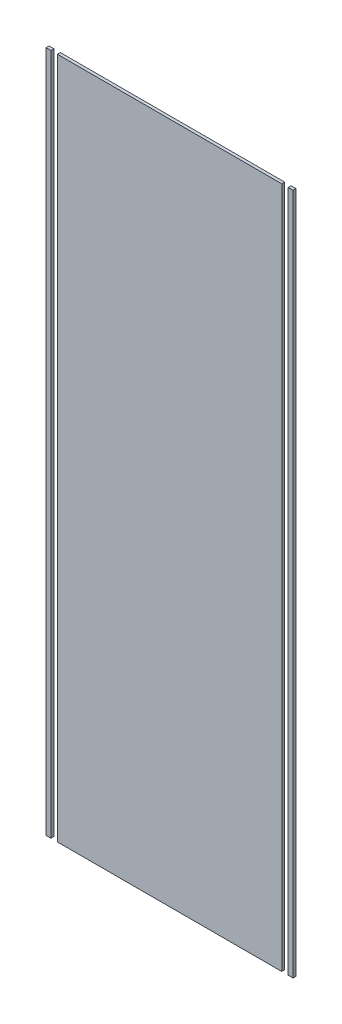
SolidWorks part; units mm, degrees
ref_plane "Спереди" through (0, 0, 0) normal (0, 0, 1) x (1, 0, 0)
ref_plane "Сверху" through (0, 0, 0) normal (0, 1, 0) x (1, 0, 0)
ref_plane "Справа" through (0, 0, 0) normal (1, 0, 0) x (0, 0, -1)
sketch "Эскиз1" plane through (0, 0, 0) normal (0, 0, 1) x (1, 0, 0)
  line L0 (1138.3, 447) -> (518, 447) construction
  line L1 (573.5, -949) -> (583.5, -949)
  line L2 (573.5, -949) -> (573.5, 447)
  line L3 (573.5, 447) -> (583.5, 447)
  line L4 (583.5, -949) -> (583.5, 447)
  line L5 (1068.8, -949) -> (1078.8, -949)
  line L6 (1068.8, -949) -> (1068.8, 447)
  line L7 (1068.8, 447) -> (1078.8, 447)
  line L8 (1078.8, -949) -> (1078.8, 447)
  line L9 (524, -949) -> (1138.3, -949) construction
  line L10 (1067.8, -680.0925) -> (1067.8, -655.0925) construction
  line L11 (596.5, -949) -> (1055.8, -949)
  line L12 (596.5, -949) -> (596.5, 447)
  line L13 (596.5, 447) -> (1055.8, 447)
  line L14 (1055.8, -949) -> (1055.8, 447)
  line L15 (584.5, -655.0925) -> (584.5, -680.0925) construction
  line L16 (595.5, -680.0925) -> (595.5, -655.0925) construction
  line L17 (1056.8, -655.0925) -> (1056.8, -680.0925) construction
  dimension "D1" = 10
  dimension "D2" = 10
  dimension "D3" = 1
  dimension "D4" = 1
  dimension "D5" = 1
  dimension "D6" = 1
extrude "Бобышка-Вытянуть1" add sketch "Эскиз1" along normal blind 6
equation "\"Толщина стенки\" = 6"
equation "\"Ширина груза\"= 420"
equation "\"Глубина груза\"= 490"
equation "\"Высота груза\"= 297"
equation "\"Ширина ячейки\"= \"Ширина груза\" + 10"
equation "\"Глубина ячейки\"= \"Глубина груза\" + 10"
equation "\"Высота ячейки\"= \"Высота груза\" + 10 + 13"
equation "\"Колво ячеек ширина\"= 2"
equation "\"Колво ячеек высота\"= 2"
equation "\"Крепление дверцы\"= 5 "
equation "\"Ширина рейки\"= \"Толщина шестерни\""
equation "\"Высота рейки\"= 20"
equation "\"Высота пола\"= \"Толщина стенки\" * 2"
equation "\"Колво полозьев\"= 5"
equation "\"Отступ рейки\"= 20"
equation "\"Глубина каретки\"= \"Глубина ячейки\" + 30 + \"Мотор Y высота корпуса\" + 20"
equation "\"Длинна рейки\"= ( \"Ширина ячейки\" + \"Толщина стенки\" + \"Крепление дверцы\" ) * \"Колво ячеек ширина\" + \"Ширина ячейки выгрузки\" * \"Колво выгрузки\" + \"Толщина стенки\""
equation "\"Отступ шпильки\"= 26"
equation "\"Диаметр шпильки\"= 5"
equation "\"Длинна шпильки\"= ( \"Высота ячейки\" + \"Толщина стенки\" + \"Высота пола\" ) * \"Колво ячеек высота\" + ( \"Толщина стенки\" + \"Отступ рейки\" ) * 2 "
equation "\"Ширина пластины\"= 50  "
equation "\"Высота зона выгрузки\"= \"Высота ячейки\" * 2 + \"Толщина стенки\" * 2"
equation "\"Колво выгрузки\"= 1"
equation "\"Ширина ячейки выгрузки\"= \"Ширина ячейки\" + \"Толщина стенки\" + \"Отступ крепления мотора фиксации\"*2"
equation "\"Отступ крепления мотора фиксации\" = 30"
equation "\"Мотор X ширина корпуса\"= 42.3"
equation "\"Мотор X высота корпуса\"= 42.3"
equation "\"Мотор X длина корпуса\"= 40"
equation "\"Мотор X вылет вала\"= 19.8"
equation "\"Мотор Y ширина корпуса\"= 42.3"
equation "\"Мотор Y высота корпуса\"= 42.3"
equation "\"Мотор Y длина корпуса\"= 48"
equation "\"Мотор Y вылет вала\"= 30"
equation "\"Мотор Z ширина корпуса\"= 42"
equation "\"Мотор Z высота корпуса\"= 42"
equation "\"Мотор Z длина корпуса\"= 40"
equation "\"Мотор Z вылет вала\"= 23"
equation "\"Мотор диаметр вала ПРЕДВ\"= 5"
equation "\"Мотор шаг крепления ПРЕДВ\"= 31"
equation "\"Мотор диаметр отверстий ПРЕДВ\"= 3"
equation "\"Мотор глубина отверстий ПРЕДВ\"= 4.5"
equation "\"Мотор диаметр буртика ПРЕДВ\"= 22"
equation "\"Мотор высота буртика ПРЕДВ\"= 2"
equation "\"Мотор диаметр шкива ПРЕДВ\"= 16"
equation "\"Мотор длина шкива ПРЕДВ\"= 12"
equation "\"Мотор отступ шкива ПРЕДВ\"= 5"
equation "\"Мотор X шаг градусов\"= 1.8"
equation "\"Мотор Y шаг градусов\"= 1.8"
equation "\"Мотор Z шаг градусов\"= 1.8"
equation "\"Мотор Y диаметр ротора\"= 25.78"
equation "\"Толщина шестерни\"= 10"
equation "\"D1@Бобышка-Вытянуть1\"=\"Толщина стенки\""
